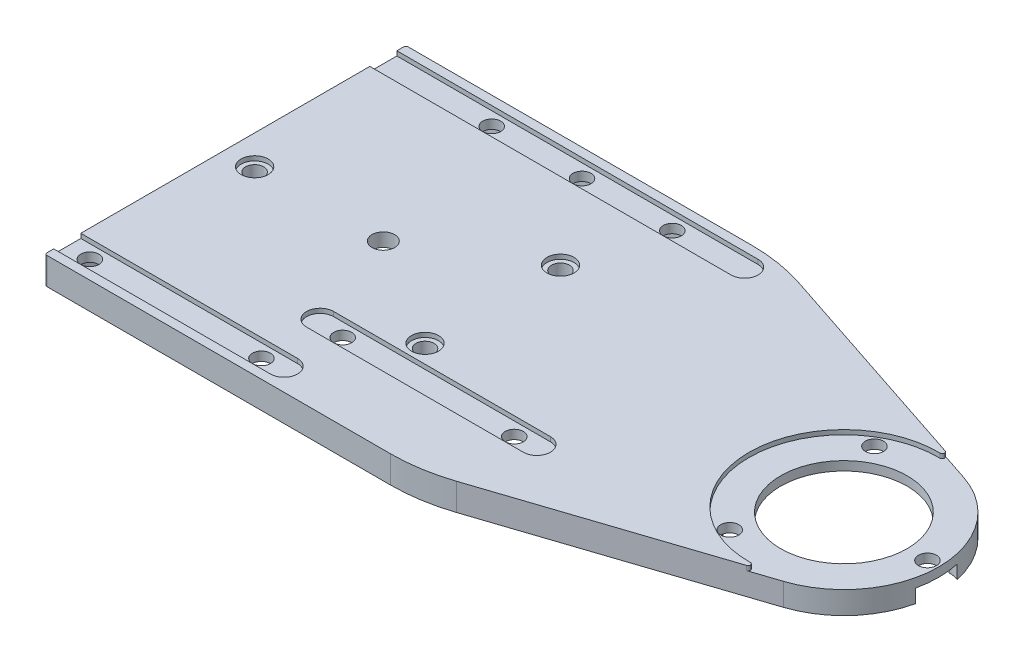
SolidWorks part; units mm, degrees
ref_plane "前视基准面" through (0, 0, 0) normal (0, 0, 1) x (1, 0, 0)
ref_plane "上视基准面" through (0, 0, 0) normal (0, 1, 0) x (1, 0, 0)
ref_plane "右视基准面" through (0, 0, 0) normal (1, 0, 0) x (0, 0, -1)
sketch "草图1" plane through (0, 0, 0) normal (0, 1, 0) x (1, 0, 0)
  line L0 (-20.9942, 0) -> (181.0483, 0) construction
  line L1 (-13, 40) -> (70, 40)
  line L2 (-13, 40) -> (-13, -40)
  line L3 (-13, -40) -> (70, -40)
  line L4 (70, 40) -> (130.6005, 19.9357)
  line L5 (0, 42.5732) -> (0, -49.2392) construction
  line L6 (124, 16.3237) -> (124, -16.3237) construction
  line L7 (70, 40) -> (130.6005, 19.9357) construction
  line L8 (70, -40) -> (130.6005, -19.9357) construction
  line L9 (70, -40) -> (130.6005, -19.9357)
  arc A0 (130.6005, -19.9357) -> (130.6005, 19.9357) centre (124, 0) ccw construction
  arc A5 (130.6005, -19.9357) -> (130.6005, 19.9357) centre (124, 0) ccw
  dimension "D5" = 42
  dimension "D7" = 42
  dimension "D1" = 13
  dimension "D2" = 40
  dimension "D3" = 40
  dimension "D4" = 124
  dimension "D9" = 70
extrude "凸台-拉伸1" add sketch "草图1" along normal blind 6
sketch "草图6" plane through (0, 6, 0) normal (0, 1, 0) x (1, 0, 0)
  line L1 (0, 0) -> (30.2712, 0) construction
  line L2 (30.2712, 0) -> (217.7288, 0) construction
  circle A0 centre (124, 0) radius 14
  dimension "D1" = 28
  dimension "D2" = 124
extrude "切除-拉伸4" cut sketch "草图6" against normal blind 10
sketch "草图7" plane through (0, 6, 0) normal (0, 1, 0) x (1, 0, 0)
  line L0 (11, 35) -> (51, 35) construction
  line L1 (0, 42.5732) -> (0, -49.2392) construction
  line L2 (-13, 40) -> (70, 40) construction
  circle A0 centre (11, 35) radius 2
  circle A1 centre (31, 35) radius 2
  circle A2 centre (51, 35) radius 2
  dimension "D1" = 4
  dimension "D2" = 11
  dimension "D3" = 5
  dimension "D4" = 20
extrude "切除-拉伸5" cut sketch "草图7" against normal blind 10
sketch "草图10" plane through (0, 6, 0) normal (0, 1, 0) x (1, 0, 0)
  line L0 (0, 0) -> (109.8479, 0) construction
  line L1 (11, 58) -> (11, -10.8563) construction
  line L2 (14, 58) -> (8, 58) construction
  line L3 (22, 0) -> (92.9812, 0) construction
  line L4 (-20.9942, 0) -> (181.0483, 0) construction
  line L5 (-6.5, 0) -> (46.2332, -15) construction
  circle A0 centre (22, 0) radius 2.5
  circle A1 centre (22, 0) radius 28.5 construction
  circle A2 centre (-6.5, 0) radius 2
  circle A3 centre (-6.5, 0) radius 3 construction
  circle A5 centre (46.2332, 15) radius 2
  circle A6 centre (46.2332, -15) radius 2
  circle A7 centre (46.2332, 15) radius 3 construction
  circle A8 centre (46.2332, -15) radius 3 construction
  dimension "D2" = 57
  dimension "D4" = 4
  dimension "D6" = 6
  dimension "D9" = 4
  dimension "D10" = 6
  dimension "D11" = 4
  dimension "D12" = 6
  dimension "D7" = 5
  dimension "D3" = 11
  dimension "D5" = 0
  dimension "D13" = 30
extrude "切除-拉伸7" cut sketch "草图10" against normal blind 10
sketch "草图11" plane through (0, 6, 0) normal (0, 1, 0) x (1, 0, 0)
  line L1 (-13, 38) -> (67, 38)
  line L2 (-13, 38) -> (-13, 32)
  line L3 (-13, 32) -> (67, 32)
  line L4 (67, 38) -> (67, 32) construction
  line L6 (70, 40) -> (-13, 40) construction
  line L7 (-13, 40) -> (-13, -40) construction
  arc A0 (67, 32) -> (67, 38) centre (67, 35) ccw
  dimension "D1" = 80
  dimension "D3" = 6
  dimension "D4" = 2
extrude "切除-拉伸8" cut sketch "草图11" against normal blind 1
sketch "草图13" plane through (0, 6, 0) normal (0, 1, 0) x (1, 0, 0)
  line L1 (-13, -38) -> (35, -38)
  line L2 (-13, -38) -> (-13, -32)
  line L3 (-13, -32) -> (35, -32)
  line L4 (35, -38) -> (35, -32) construction
  line L6 (-13, -40) -> (70, -40) construction
  line L7 (-13, 40) -> (-13, -40) construction
  arc A0 (35, -38) -> (35, -32) centre (35, -35) ccw
  dimension "D4" = 3
  dimension "D1" = 6
  dimension "D2" = 2
  dimension "D3" = 48
extrude "切除-拉伸9" cut sketch "草图13" against normal blind 1
sketch "草图14" plane through (0, 6, 0) normal (0, 1, 0) x (1, 0, 0)
  line L0 (-13, -40) -> (70, -40) construction
  line L1 (78, -25) -> (30, -25)
  line L2 (78, -25) -> (78, -19) construction
  line L3 (78, -19) -> (30, -19)
  line L4 (30, -25) -> (30, -19) construction
  line L5 (-13, 40) -> (-13, -40) construction
  arc A0 (78, -25) -> (78, -19) centre (78, -22) ccw
  arc A1 (30, -19) -> (30, -25) centre (30, -22) ccw
  dimension "D1" = 15
  dimension "D2" = 6
  dimension "D3" = 43
  dimension "D4" = 48
extrude "切除-拉伸10" cut sketch "草图14" against normal blind 1
sketch "草图16" plane through (0, 6, 0) normal (0, 1, 0) x (1, 0, 0)
  circle A0 centre (124, 0) radius 18.5 construction
  circle A1 centre (142.5, 0) radius 2
  circle A3 centre (114.75, -16.0215) radius 2
  circle A4 centre (114.75, 16.0215) radius 2
  point P12 (124, 0)
  dimension "D1" = 37
  dimension "D2" = 4
  dimension "D3" = 3
extrude "切除-拉伸11" cut sketch "草图16" against normal blind 10
sketch "草图17" plane through (0, 6, 0) normal (0, 1, 0) x (1, 0, 0)
  circle A0 centre (-8, -35) radius 2
  circle A1 centre (30, -35) radius 2
  circle A2 centre (35, -22) radius 2
  circle A3 centre (73, -22) radius 2
  dimension "D1" = 4
extrude "切除-拉伸12" cut sketch "草图17" against normal blind 10
sketch "草图18" plane through (0, 0, 0) normal (0, -1, 0) x (-1, 0, 0)
  line L0 (20.9942, 0) -> (-181.0483, 0) construction
  line L1 (11, 38) -> (-19, 38)
  line L2 (11, 38) -> (11, -1)
  line L4 (-19, 38) -> (-19, 19.2678)
  line L5 (13, -40) -> (-70, -40) construction
  line L6 (11, -38) -> (-19, -38)
  line L7 (11, -38) -> (11, -1)
  line L9 (-19, -38) -> (-19, -19.2678)
  line L10 (13, 40) -> (13, -40) construction
  line L11 (13, 40) -> (-70, 40) construction
  line L12 (-57, -38) -> (-69.6775, -38)
  line L13 (-21, 38) -> (-55, 38)
  line L14 (-21, 38) -> (-21, 19.4743)
  line L16 (-55, 38) -> (-55, 1)
  line L17 (-55, -38) -> (-21, -38)
  line L18 (-55, -38) -> (-55, -1)
  line L19 (-55, -1) -> (-41.4743, -1)
  line L20 (-21, -38) -> (-21, -19.4743)
  line L21 (-69.6775, -38) -> (-129.9719, -18.0371)
  line L22 (-70, 40) -> (-130.6005, 19.9357) construction
  line L23 (-55, 1) -> (-41.4743, 1)
  line L24 (-57, -13.5) -> (-57, -38)
  line L26 (-57, -11.5) -> (-106.4287, -11.5)
  line L27 (-57, -11.5) -> (-57, 11.5)
  line L28 (-57, 11.5) -> (-106.4287, 11.5)
  line L29 (-110.6303, -13.5) -> (-57, -13.5)
  line L30 (-124, 0) -> (-83.5288, 0) construction
  line L31 (-70, -40) -> (-93.8395, -32.1069) construction
  line L32 (-70, -40) -> (-130.6005, -19.9357) construction
  line L34 (-57, 13.5) -> (-57, 38)
  line L35 (-57, 38) -> (-69.6775, 38)
  line L36 (-69.6775, 38) -> (-129.9719, 18.0371)
  line L37 (-110.6303, 13.5) -> (-57, 13.5)
  circle A0 centre (-22, 0) radius 17.5
  arc A1 (-2.59, 1.8715) -> (-19, 19.2678) centre (-22, 0) ccw
  arc A2 (-106.4287, -11.5) -> (-106.4287, 11.5) centre (-124, 0) ccw
  arc A3 (-21, 19.4743) -> (-41.4743, 1) centre (-22, 0) ccw
  arc A4 (-41.4743, -1) -> (-21, -19.4743) centre (-22, 0) ccw
  arc A5 (-19, -19.2678) -> (-2.59, 1.8715) centre (-22, 0) ccw
  arc A7 (-129.9719, -18.0371) -> (-110.6303, -13.5) centre (-124, 0) ccw
  arc A8 (-110.6303, 13.5) -> (-129.9719, 18.0371) centre (-124, 0) ccw
  dimension "D2" = 35
  dimension "D3" = 39
  dimension "D26" = 42
  dimension "D30" = 2
  dimension "D1" = 22
  dimension "D4" = 2
  dimension "D7" = 2
  dimension "D8" = 2
  dimension "D10" = 30
  dimension "D11" = 30
  dimension "D12" = 2
  dimension "D13" = 2
  dimension "D14" = 2
  dimension "D15" = 2
  dimension "D16" = 2
  dimension "D17" = 1
  dimension "D18" = 34
  dimension "D19" = 34
  dimension "D20" = 2
  dimension "D21" = 2
  dimension "D22" = 4
  dimension "D23" = 23
  dimension "D24" = 2
  dimension "D25" = 2
  dimension "D31" = 2
extrude "切除-拉伸13" cut sketch "草图18" against normal blind 3
fillet "圆角1" radius 4 2 edges at (57, 1.5, 11.5) (57, 1.5, -11.5)
fillet "圆角2" radius 4 12 edges at (19, 1.5, -38) (-11, 1.5, -38) (21, 1.5, -38) (57, 1.5, -38) (57, 1.5, -13.5) (55, 1.5, -38) (55, 1.5, 1) (21, 1.5, 38) (55, 1.5, 38) (69.6775, 1.5, 38) (57, 1.5, 38) (57, 1.5, 13.5)
fillet "圆角3" radius 3 1 edges at (-11, 1.5, 38)
sketch "草图19" plane through (0, 0, 0) normal (0, -1, 0) x (1, 0, 0)
  circle A0 centre (114.75, 16.0215) radius 5
  circle A1 centre (142.5, 0) radius 5
  circle A2 centre (114.75, -16.0215) radius 5
  dimension "D1" = 10
extrude "切除-拉伸14" cut sketch "草图19" against normal blind 3
sketch "草图20" plane through (0, 0, 0) normal (0, -1, 0) x (1, 0, 0)
  circle A0 centre (124, 0) radius 14
  circle A1 centre (124, 0) radius 19
  dimension "D1" = 38
  dimension "D2" = 28
extrude "切除-拉伸15" cut sketch "草图20" against normal blind 3
sketch "草图21" plane through (0, 6, 0) normal (0, 1, 0) x (1, 0, 0)
  circle A0 centre (-6.5, 0) radius 3
  circle A1 centre (46.2332, 15) radius 3
  circle A2 centre (46.2332, -15) radius 3
  dimension "D1" = 6
  dimension "D2" = 6
  dimension "D3" = 6
extrude "切除-拉伸16" cut sketch "草图21" against normal blind 1
sketch "草图22" plane through (0, 3, 0) normal (0, -1, 0) x (1, 0, 0)
  circle A0 centre (46.2332, 15) radius 2
  circle A1 centre (46.2332, 15) radius 5
  circle A2 centre (46.2332, -15) radius 2
  circle A3 centre (46.2332, -15) radius 5
  circle A4 centre (-6.5, 0) radius 2
  circle A5 centre (-6.5, 0) radius 5
  dimension "D1" = 10
  dimension "D2" = 10
  dimension "D3" = 10
extrude "凸台-拉伸2" add sketch "草图22" along normal blind 3
fillet "圆角6" radius 4 1 edges at (19, 1.5, 38)
fillet "圆角7" radius 4 1 edges at (55, 1.5, -1)
fillet "圆角8" radius 0.5 2 edges at (-13, 3, -40) (-13, 3, 40)
fillet "圆角9" radius 40 2 edges at (70, 3, 40) (70, 3, -40)
fillet "圆角10" radius 4 6 edges at (21, 1.5, 19.4743) (19, 1.5, 19.2678) (19, 1.5, -19.2678) (21, 1.5, -19.4743) (41.4743, 1.5, -1) (41.4743, 1.5, 1)
fillet "圆角11" radius 3 2 edges at (106.4287, 1.5, 11.5) (106.4287, 1.5, -11.5)
fillet "圆角12" radius 4 1 edges at (69.6775, 1.5, -38)
fillet "圆角13" radius 3 1 edges at (-11, 1.5, -2.1794)
sketch "草图23" plane through (0, 6, 0) normal (0, 1, 0) x (1, 0, 0)
  circle A0 centre (124, 0) radius 21
  dimension "D1" = 42
extrude "切除-拉伸17" cut sketch "草图23" against normal blind 1
fillet "圆角14" radius 0.5 2 edges at (130.6005, 5.5, 19.9357) (130.6005, 5.5, -19.9357)
sketch "草图24" plane through (0, 3, 0) normal (0, -1, 0) x (1, 0, 0)
  line L0 (-6.5, 0) -> (9.7491, 0) construction
  line L1 (22, 0) -> (46.2332, 15) construction
  line L2 (46.2332, 15) -> (60.0619, 15) construction
  line L3 (-1.5251, 0.5) -> (2.5064, 0.5)
  line L4 (-1.5251, -0.5) -> (2.5064, -0.5)
  line L5 (38.312, 10.6849) -> (41.7399, 12.8068)
  line L6 (42.2663, 11.9565) -> (38.8383, 9.8346)
  line L7 (51.2082, 14.5) -> (55, 14.5)
  line L8 (55, 14.5) -> (55, 15.5)
  line L9 (55, 15.5) -> (51.2082, 15.5)
  line L10 (55, 5) -> (55, 34) construction
  arc A0 (-1.5251, -0.5) -> (-1.5251, 0.5) centre (-6.5, 0) ccw
  arc A1 (38.8383, 9.8346) -> (38.312, 10.6849) centre (22, 0) ccw
  arc A2 (51.2082, 14.5) -> (51.2082, 15.5) centre (46.2332, 15) ccw
  arc A3 (2.5064, 0.5) -> (2.5064, -0.5) centre (22, 0) ccw
  arc A4 (41.7399, 12.8068) -> (42.2663, 11.9565) centre (46.2332, 15) ccw
  dimension "D4" = 10
  dimension "D5" = 39
  dimension "D6" = 10
  dimension "D1" = 1
  dimension "D2" = 1
  dimension "D3" = 1
extrude "凸台-拉伸3" add sketch "草图24" along normal blind 3
fillet "圆角15" radius 3 12 edges at (38.312, 1.5, 10.6849) (41.7399, 1.5, 12.8068) (55, 1.5, 15.5) (51.2082, 1.5, 15.5) (55, 1.5, 14.5) (51.2082, 1.5, 14.5) (38.8383, 1.5, 9.8346) (42.2663, 1.5, 11.9565) (2.5064, 1.5, 0.5) (-1.5251, 1.5, 0.5) (2.5064, 1.5, -0.5) (-1.5251, 1.5, -0.5)
mirror "镜向2" about plane through (0, 0, 0) normal (0, 0, 1) of "凸台-拉伸3"
fillet "圆角16" radius 3 8 edges at (38.8383, 1.5, -9.8346) (42.2663, 1.5, -11.9565) (55, 1.5, -14.5) (51.2082, 1.5, -14.5) (55, 1.5, -15.5) (51.2082, 1.5, -15.5) (41.7399, 1.5, -12.8068) (38.312, 1.5, -10.6849)
